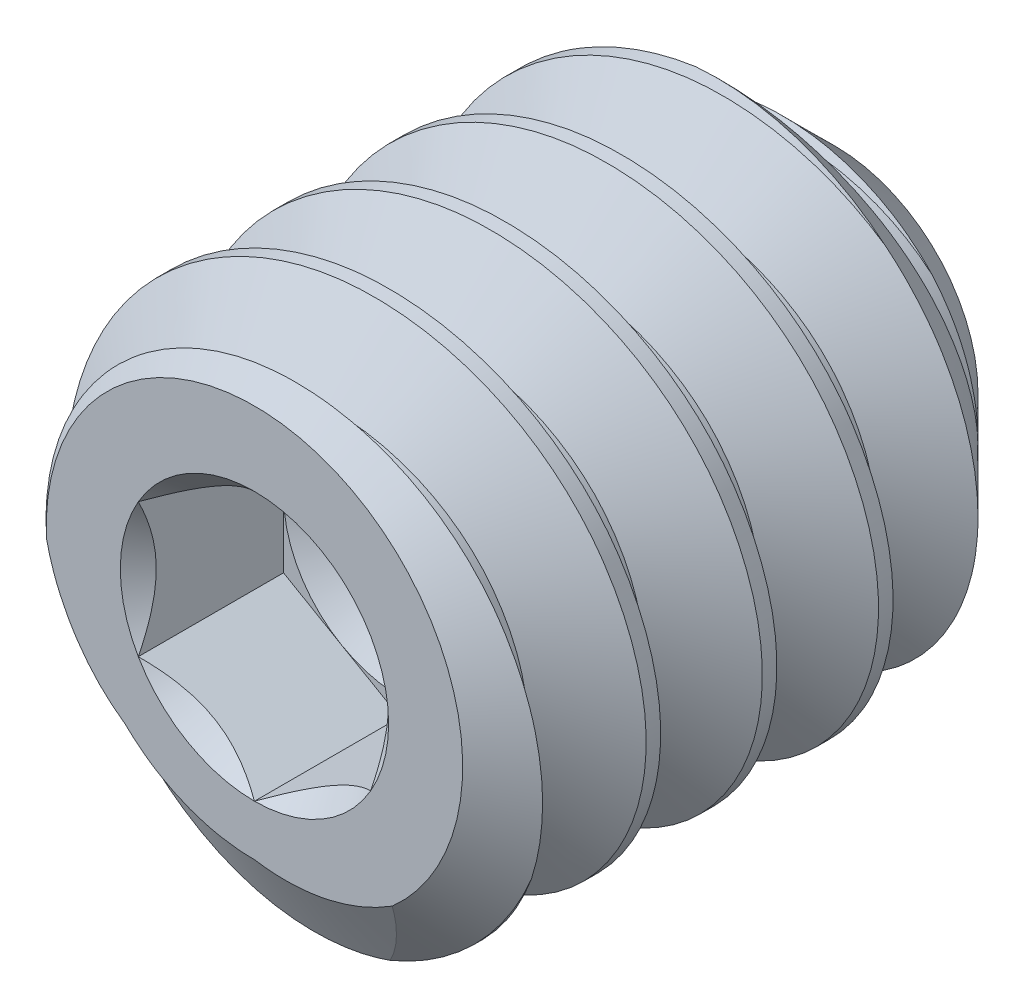
SolidWorks part; units mm, degrees
ref_plane "Front" through (0, 0, 0) normal (0, 0, 1) x (1, 0, 0)
ref_plane "Top" through (0, 0, 0) normal (0, 1, 0) x (1, 0, 0)
ref_plane "Right" through (0, 0, 0) normal (1, 0, 0) x (0, 0, -1)
sketch "Sketch22" plane through (0, 0, 0) normal (1, 0, 0) x (0, 0, -1)
  line L0 (-1.3533, 0) -> (-1.3533, 1.1379)
  line L1 (-1.3533, 1.1379) -> (-1.1541, 1.4224)
  line L2 (-1.1541, 1.4224) -> (1.1787, 1.4224)
  line L3 (1.1787, 1.4224) -> (1.8217, 0.7794)
  line L4 (1.8217, 0.7794) -> (1.3533, 0)
  line L5 (1.3533, 0) -> (-1.3533, 0)
  line L6 (1.3533, 0) -> (1.8217, 0) construction
  line L7 (1.8217, 0) -> (1.8217, 0.7794) construction
  line L8 (1.8217, -0.7794) -> (1.3533, 0) construction
  line L9 (-1.1541, -1.4224) -> (1.1787, -1.4224) construction
  dimension "Dia" = 2.8448
  dimension "Length" = 3.175
  dimension "D3" = 35
  dimension "D5" = 118
  dimension "D6" = 45
  dimension "D7" = 2.2758
revolve "Revolve1" add sketch "Sketch22" angle 360 about L6
ref_plane "Plane1" through (0, 0, -1.8217) normal (0, 0, 1) x (1, 0, 0)
sketch "Sketch27" plane through (0, 0, -1.8217) normal (0, 0, 1) x (1, 0, 0)
  circle A0 centre (0, 0) radius 1.4224 construction
  circle A1 centre (0, 0) radius 1.4224
curve "Helix/Spiral1" pitch 0.635 height 3.81 radius 1.4224 centre (0, 0, -1.8217) axis (0, 0, 1) start towards (0, 1, 0)
sketch "Sketch28" plane through (0, 0, 0) normal (1, 0, 0) x (0, 0, -1)
  line L0 (1.8217, 1.4224) -> (2.3773, 1.4224)
  line L1 (2.3773, 1.4224) -> (2.1392, 1.01)
  line L2 (2.1392, 1.01) -> (2.0598, 1.01)
  line L3 (2.0598, 1.01) -> (1.8217, 1.4224)
  line L4 (1.9407, 1.2162) -> (2.2582, 1.2162) construction
  line L6 (-1.1541, 1.4224) -> (1.1787, 1.4224) construction
  line L7 (1.8217, 1.5646) -> (1.8217, -1.5646) construction
  dimension "D1" = 0.0794
  dimension "D3" = 60
  dimension "D2" = 0.3175
sweep "Cut-Sweep2" cut profiles "Sketch28" path "Helix/Spiral1" align with end faces yes
sketch "Sketch23" plane through (0, 0, 1.3533) normal (0, 0, 1) x (1, 0, 0)
  line L1 (0, 0.7332) -> (-0.635, 0.3666)
  line L2 (-0.635, 0.3666) -> (-0.635, -0.3666)
  line L3 (-0.635, -0.3666) -> (0, -0.7332)
  line L4 (0, -0.7332) -> (0.635, -0.3666)
  line L5 (0.635, -0.3666) -> (0.635, 0.3666)
  line L6 (0.635, 0.3666) -> (0, 0.7332)
  circle A0 centre (0, 0) radius 0.635 construction
  dimension "Hex" = 1.27
extrude "Cut-Extrude10" cut sketch "Sketch23" against normal blind 0.7937
sketch "Sketch24" plane through (0, 0, 1.3533) normal (0, 0, 1) x (1, 0, 0)
  circle A0 centre (0, 0) radius 0.7332
extrude "Cut-Extrude11" cut sketch "Sketch24" against normal through all draft 45
sketch "Sketch26" plane through (0, 0, 0.5596) normal (0, 0, 1) x (1, 0, 0)
  circle A0 centre (0, 0) radius 0.635 construction
  circle A1 centre (0, 0) radius 0.635
extrude "Cut-Extrude12" cut sketch "Sketch26" against normal through all draft 60
sketch "Sketch30" plane through (0, 0, 0) normal (1, 0, 0) x (0, 0, -1)
  line L0 (-1.1541, 1.4224) -> (1.1787, 1.4224) construction
  line L1 (-1.3533, 0) -> (-1.3533, 1.1379) construction
  line L2 (1.8217, 0) -> (1.8217, 0.7794) construction
  line L3 (-1.1541, -1.4224) -> (1.1787, -1.4224) construction
  point P0 (-1.3533, 1.4224)
  point P1 (1.8217, 1.4224)
  point P2 (1.8217, -1.4224)
  point P11 (0.2342, -1.4224)
  dimension "D1" = 1.5875
sketch "Sketch31" plane through (0, 0, 0) normal (1, 0, 0) x (0, 0, -1)
  line L2 (1.3533, 0) -> (1.8217, -0.7794)
  line L3 (1.8217, 0.7794) -> (1.3533, 0)
equation "\"D7@Sketch22\"=\"Dia@Sketch22\"*.8"
equation "\"D1@Sketch28\" = \"D4@Helix/Spiral1\" * .125"
equation "\"D3@Helix/Spiral1\" = \"Length@Sketch22\" + \"D4@Helix/Spiral1\""
equation "\"D1@Sketch30\" = \"D4@Helix/Spiral1\" * 2.5"
equation "\"hex Depth@Cut-Extrude10\" = \"Hex@Sketch23\" * .625"
equation "\"D2@Sketch28\" = \"D4@Helix/Spiral1\" * .5"
